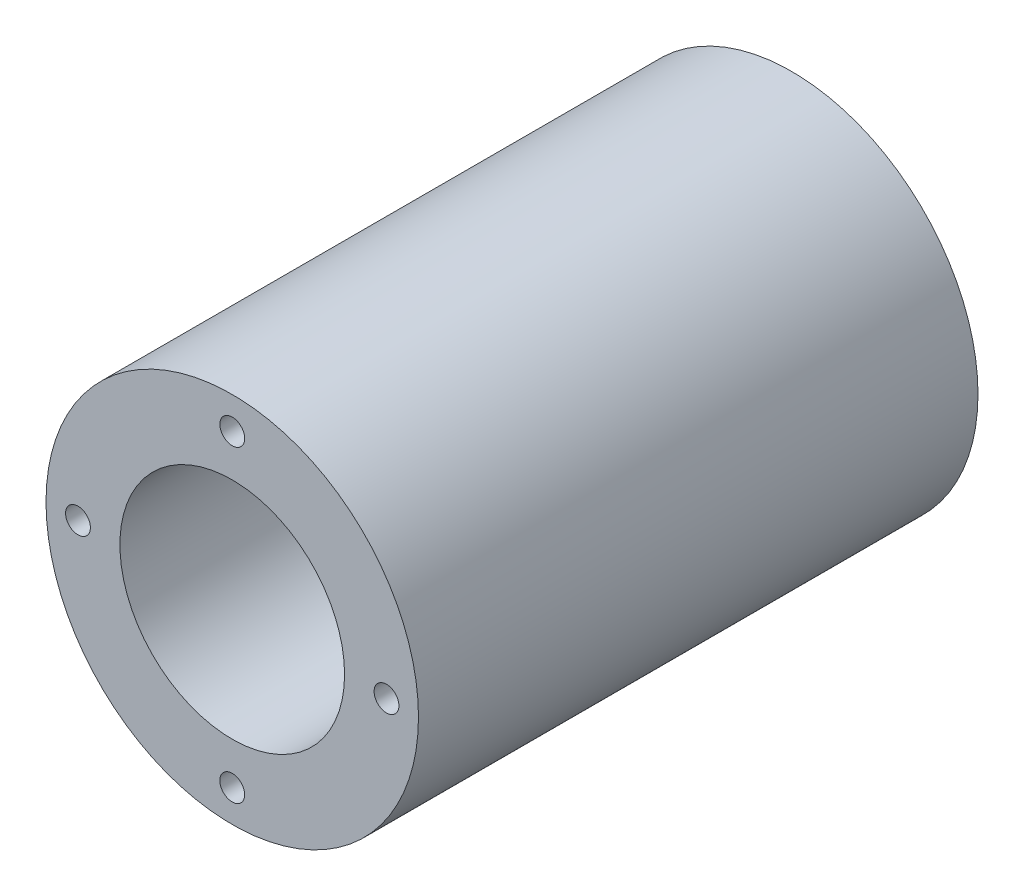
SolidWorks part; units mm, degrees
material "6061-T6 (SS)"
ref_plane "Front Plane" through (0, 0, 0) normal (0, 0, 1) x (1, 0, 0)
ref_plane "Top Plane" through (0, 0, 0) normal (0, 1, 0) x (1, 0, 0)
ref_plane "Right Plane" through (0, 0, 0) normal (1, 0, 0) x (0, 0, -1)
sketch "Sketch Spindle Skeleton" plane through (0, 0, 0) normal (1, 0, 0) x (0, 0, -1)
  line L0 (-108, -9.5) -> (-149, -9.5)
  line L5 (-1000, 0) -> (49000, 0)
  line L6 (0, -9.5) -> (0, 9.5)
  line L13 (0, 9.5) -> (-46.4, 9.5)
  line L26 (-46.4, 9.5) -> (-46.4, 14)
  line L27 (-46.4, 14) -> (-108, 14)
  line L32 (-108, 14) -> (-108, 9.5)
  line L34 (-165, 7) -> (-165, -7)
  line L36 (-108, -9.5) -> (-108, -14)
  line L37 (-108, -14) -> (-46.4, -14)
  line L38 (-46.4, -14) -> (-46.4, -9.5)
  line L39 (0, -9.5) -> (-46.4, -9.5)
  line L40 (-22.625, 37.5) -> (-13.625, 37.5)
  line L41 (-124.6, 22.6187) -> (-108, 22.6187)
  line L42 (-124.6, 22.6187) -> (-124.6, -22.6187)
  line L43 (-124.6, -22.6187) -> (-108, -22.6187)
  line L44 (-108, 22.6187) -> (-108, -22.6187)
  line L45 (-124.6, 22.6187) -> (-108, -22.6187) construction
  line L46 (-124.6, -22.6187) -> (-108, 22.6187) construction
  line L47 (-29.8, 22.6187) -> (-46.4, 22.6187)
  line L48 (-29.8, 22.6187) -> (-29.8, -22.6187)
  line L49 (-29.8, -22.6187) -> (-46.4, -22.6187)
  line L50 (-46.4, 22.6187) -> (-46.4, -22.6187)
  line L51 (-29.8, 22.6187) -> (-46.4, -22.6187) construction
  line L52 (-29.8, -22.6187) -> (-46.4, 22.6187) construction
  line L59 (-13.625, 37.5) -> (-13.625, -37.5)
  line L60 (-13.625, -37.5) -> (-22.625, -37.5)
  line L61 (-22.625, -22.6187) -> (-26.625, -22.6187)
  line L62 (-26.625, -22.6187) -> (-26.625, -12.5)
  line L63 (-26.625, -12.5) -> (-22.625, -12.5)
  line L64 (-22.625, -12.5) -> (-22.625, 12.5)
  line L65 (-22.625, 12.5) -> (-26.625, 12.5)
  line L66 (-26.625, 12.5) -> (-26.625, 22.6187)
  line L67 (-26.625, 22.6187) -> (-22.625, 22.6187)
  line L68 (-22.625, 22.6187) -> (-22.625, 37.5)
  line L69 (-22.625, -22.6187) -> (-22.625, -37.5)
  line L71 (-136.284, 37.5) -> (-23.625, 37.5)
  line L72 (-136.284, 37.5) -> (-136.284, -37.5)
  line L73 (-136.284, -37.5) -> (-23.625, -37.5)
  line L74 (-23.625, 37.5) -> (-23.625, -37.5)
  line L75 (-136.284, 37.5) -> (-23.625, -37.5) construction
  line L76 (-136.284, -37.5) -> (-23.625, 37.5) construction
  line L77 (-149, -9.5) -> (-149, -7)
  line L78 (-149, -7) -> (-165, -7)
  line L79 (-108, 9.5) -> (-149, 9.5)
  line L80 (-149, 7) -> (-165, 7)
  line L81 (-149, 9.5) -> (-149, 7)
  line L82 (-128.5, 9.5) -> (-128.5, -9.5) construction
  line L83 (-23.2, 9.5) -> (-23.2, -9.5) construction
  line L96 (-136.284, 37.5) -> (-145.284, 37.5)
  line L98 (-136.284, -37.5) -> (-145.284, -37.5)
  line L99 (-145.284, 37.5) -> (-145.284, -37.5)
  line L110 (-136.284, 37.5) -> (-136.284, -37.5)
  point P3 (0, 0)
  point P18 (-116.3, 0)
  point P24 (-38.1, 0)
  point P29 (-79.9545, 0)
  point P48 (-13.625, 31.0593)
  point P70 (-145.284, 31.0593)
sketch "Sketch1" plane through (0, 0, 0) normal (1, 0, 0) x (0, 0, -1)
  line L0 (-23.625, 37.5) -> (-23.625, -37.5) construction
  line L1 (-136.284, -37.5) -> (-23.625, -37.5) construction
  line L2 (-136.284, 37.5) -> (-136.284, -37.5) construction
  line L3 (-136.284, 37.5) -> (-23.625, 37.5) construction
  line L4 (-23.625, 37.5) -> (-23.625, -37.5)
  line L5 (-136.284, -37.5) -> (-23.625, -37.5)
  line L6 (-136.284, 37.5) -> (-136.284, -37.5)
  line L7 (-136.284, 37.5) -> (-23.625, 37.5)
  line L8 (-26.625, 22.6187) -> (-22.625, 22.6187) construction
  line L10 (-136.284, 22.6187) -> (-23.625, 22.6187)
  line L15 (-136.284, 0) -> (-23.625, 0) construction
revolve "Revolve1" add sketch "Sketch1" angle 360 about L15 region at (0, 30.0594, 79.9545)
sketch "Back Hole Top Location" plane through (0, 0, 23.625) normal (0, 0, -1) x (-1, 0, 0)
  point P9 (0, 31.0593)
hole_wizard "M6x1.0 Tapped Hole3" positions "Sketch8" profile "Sketch9" tap size "M6x1.0" standard "ANSI Metric"
sketch "Sketch8" plane through (0, 0, 23.625) normal (0, 0, -1) x (-1, 0, 0)
  point P0 (0, 31.0593)
sketch "Sketch9" plane through (0, 31.0593, 23.625) normal (1, 0, 0) x (0, 1, 0)
  line L0 (0, 0) -> (0, 16.5022)
  line L1 (0, 16.5022) -> (2.5, 15)
  line L2 (2.5, 15) -> (2.5, 0)
  line L5 (2.5, 0) -> (0, 0)
  line L10 (0, 16.5022) -> (-2.5, 15) construction
  line L11 (0, -6.35) -> (0, 107.95) construction
  dimension "Tap Drill Dia." = 5
  dimension "Tap Drill Depth" = 15
  dimension "Drill Angle" = 118
pattern_circular "BackFacePattern" count 6 over 360 about axis through (0, 0, 1000) along (0, 0, -1) of "M6x1.0 Tapped Hole3"
ref_plane "Midplane" through (0, 0, 79.9545) normal (0, 0, -1) x (-1, 0, 0)
sketch "Front Hole Top Location" plane through (0, 0, 136.284) normal (0, 0, 1) x (1, 0, 0)
  point P0 (0, 31.0593)
hole_wizard "M6x1.0 Tapped Hole2" positions "Sketch5" profile "Sketch6" tap size "M6x1.0" standard "ANSI Metric"
sketch "Sketch5" plane through (0, 0, 136.284) normal (0, 0, 1) x (1, 0, 0)
  point P0 (0, 31.0593)
sketch "Sketch6" plane through (0, 31.0593, 136.284) normal (1, 0, 0) x (0, -1, 0)
  line L0 (0, 0) -> (0, 16.5022)
  line L1 (0, 16.5022) -> (2.5, 15)
  line L2 (2.5, 15) -> (2.5, 0)
  line L5 (2.5, 0) -> (0, 0)
  line L10 (0, 16.5022) -> (-2.5, 15) construction
  line L11 (0, -6.35) -> (0, 107.95) construction
  dimension "Tap Drill Dia." = 5
  dimension "Tap Drill Depth" = 15
  dimension "Drill Angle" = 118
pattern_circular "FrontFacePattern" count 4 over 360 about axis through (0, 0, 1000) along (0, 0, -1) of "M6x1.0 Tapped Hole2"
sketch "Sketch7" plane through (0, 0, 23.625) normal (0, 0, -1) x (-1, 0, 0)
  circle A0 centre (0, 0) radius 26.9875
  circle A1 centre (0, 0) radius 24.6062
  dimension "D1" = 53.975
  dimension "D2" = 49.2125
extrude "Cut-Extrude1" cut sketch "Sketch7" against normal blind 0.5
